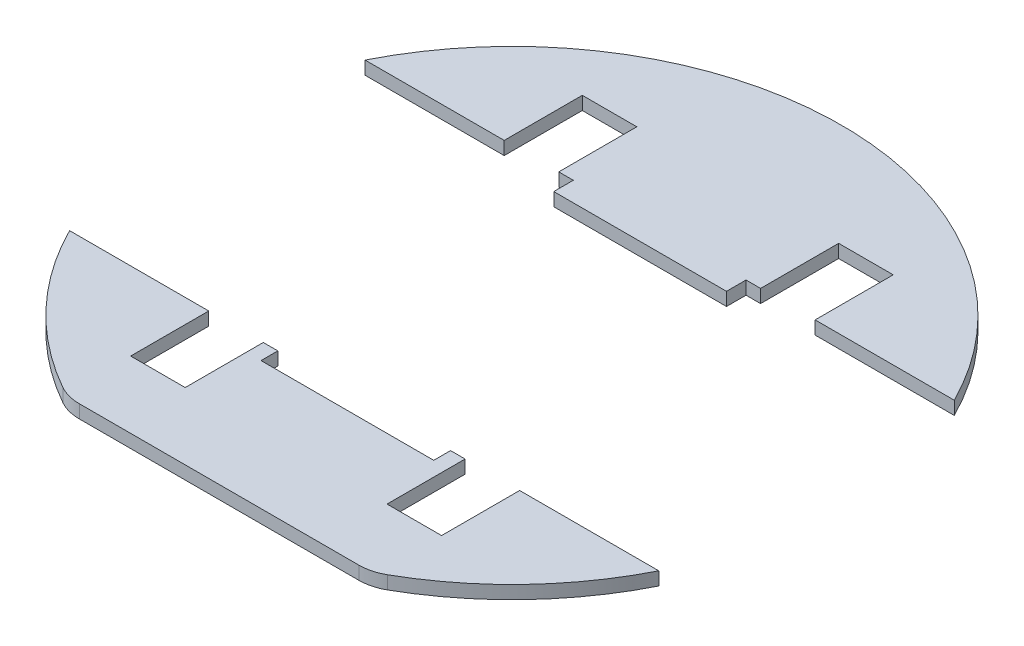
SolidWorks part; units mm, degrees
ref_plane "Front Plane" through (0, 0, 0) normal (0, 0, 1) x (1, 0, 0)
ref_plane "Top Plane" through (0, 0, 0) normal (0, 1, 0) x (1, 0, 0)
ref_plane "Right Plane" through (0, 0, 0) normal (1, 0, 0) x (0, 0, -1)
sketch "Sketch1" plane through (0, 0, 0) normal (0, 1, 0) x (1, 0, 0)
  line L0 (-30.7634, -64.4046) -> (30.7634, -64.4046)
  line L1 (0, -83.2398) -> (0, 0) construction
  line L2 (0, -83.2398) -> (33.2911, -64.4046) construction
  arc A0 (35.6856, -63.1093) -> (-35.6856, -63.1093) centre (0, 0) ccw
  circle A1 centre (0, -83.2398) radius 38.25 construction
  arc A2 (30.7634, -64.4046) -> (35.6856, -63.1093) centre (30.7634, -54.4046) ccw
  arc A3 (-30.7634, -64.4046) -> (-35.6856, -63.1093) centre (-30.7634, -54.4046) cw
  dimension "D1" = 145
  dimension "D2" = 76.5
  dimension "D4" = 10
  dimension "D3" = 60.5
extrude "Boss-Extrude1" add sketch "Sketch1" along normal blind 2.9
sketch "Sketch2" plane through (0, 2.9, 0) normal (0, 1, 0) x (1, 0, 0)
  line L0 (18, -36.2) -> (-18, -36.2) construction
  line L1 (-34.2, -49.6757) -> (-22.2, -49.6757)
  line L2 (-34.2, -49.6757) -> (-34.2, 49.6757)
  line L3 (-34.2, 49.6757) -> (-22.2, 49.6757)
  line L4 (-22.2, -49.6757) -> (-22.2, -32.5)
  line L5 (-19, -32.5) -> (-22.2, -32.5) construction
  line L6 (-22.2, -49.6757) -> (-22.2, -32.5)
  line L7 (-19, -32.5) -> (-22.2, -32.5)
  line L8 (19, 28.2) -> (-19, 28.2) construction
  line L9 (18, -36.2) -> (-18, -36.2)
  line L10 (-19, 32.5) -> (-22.2, 32.5) construction
  line L11 (-19, 32.5) -> (-22.2, 32.5)
  line L12 (19, 28.2) -> (-19, 28.2)
  line L13 (-19, -32.5) -> (-19, -36.2)
  line L14 (-19, -36.2) -> (-18, -36.2)
  line L15 (-19, 32.5) -> (-19, 28.2)
  line L16 (-22.2, 32.5) -> (-22.2, 49.6757)
  line L17 (0, 0) -> (0, -64.4046) construction
  line L18 (-30.7634, -64.4046) -> (30.7634, -64.4046) construction
  line L19 (22.2, 32.5) -> (22.2, 49.6757)
  line L20 (19, 32.5) -> (19, 28.2)
  line L21 (19, -36.2) -> (18, -36.2)
  line L22 (19, -32.5) -> (19, -36.2)
  line L23 (19, 32.5) -> (22.2, 32.5)
  line L24 (19, -32.5) -> (22.2, -32.5)
  line L25 (22.2, -49.6757) -> (22.2, -32.5)
  line L26 (22.2, -49.6757) -> (22.2, -32.5)
  line L27 (34.2, 49.6757) -> (22.2, 49.6757)
  line L28 (34.2, -49.6757) -> (34.2, 49.6757)
  line L29 (34.2, -49.6757) -> (22.2, -49.6757)
extrude "Cut-Extrude1" cut sketch "Sketch2" against normal through all contours L29 L28 L27 L19 L23 L20 L12 L15 L11 L16 L3 L2 L1 L4 L7 L13 L14 L9 L21 L22 L24 L25 region at (0, 2.9, 1.8654)
sketch "Sketch3" plane through (0, 2.9, 0) normal (0, 1, 0) x (1, 0, 0)
  line L0 (-34.2, 32.5) -> (-34.2, -32.5)
  line L1 (-72.5, -32.5) -> (-34.2, -32.5)
  line L2 (-72.5, -32.5) -> (-72.5, 32.5)
  line L3 (-72.5, 32.5) -> (-34.2, 32.5)
  line L4 (72.5, -32.5) -> (72.5, 32.5)
  line L5 (-72.5, -32.5) -> (72.5, 32.5) construction
  line L6 (-72.5, 32.5) -> (72.5, -32.5) construction
  line L7 (-34.2, -49.6757) -> (-34.2, 49.6757) construction
  line L8 (34.2, 32.5) -> (34.2, -32.5)
  line L9 (34.2, -49.6757) -> (34.2, 49.6757) construction
  line L10 (34.2, 32.5) -> (72.5, 32.5)
  line L11 (34.2, -32.5) -> (72.5, -32.5)
  arc A0 (35.6856, -63.1093) -> (-35.6856, -63.1093) centre (0, 0) ccw construction
  point P0 (0, 0)
  dimension "D1" = 65
extrude "Cut-Extrude2" cut sketch "Sketch3" against normal through all
equation "\"smallPulleyTeeth\"= 15"
equation "\"largePulleyTeeth\"= 30"
equation "\"eighthThick\"= 2.9mm"
equation "\"sixteenthThick\" = 1.7mm"
equation "\"quarterThick\"=6.0mm"
equation "\"OD\" = 145mm"
equation "\"puckAngle\" = 60.5deg"
equation "\"puckDiam\" = 76.5mm"
equation "\"axlePress\" = 5.9mm"
equation "\"press\" = 0.2mm"
equation "\"wheelClear\" = 0.3mm"
equation "\"10-32clear\" = 4.8mm"
equation "\"6-32clear\" = 3.3mm"
equation "\"8-32clear\" = 4.0mm"
equation "\"4-40clear\" = 3.0mm"
equation "\"wheelHeight\" = 22mm"
equation "\"wheelWell\" = 65mm"
equation "\"D1@Sketch1\"=\"OD\""
equation "\"D1@Boss-Extrude1\"=\"eighthThick\""
equation "\"D2@Sketch1\"=\"puckDiam\""
equation "\"D3@Sketch1\"=\"puckAngle\""
equation "\"D1@Sketch3\"=\"wheelWell\""
